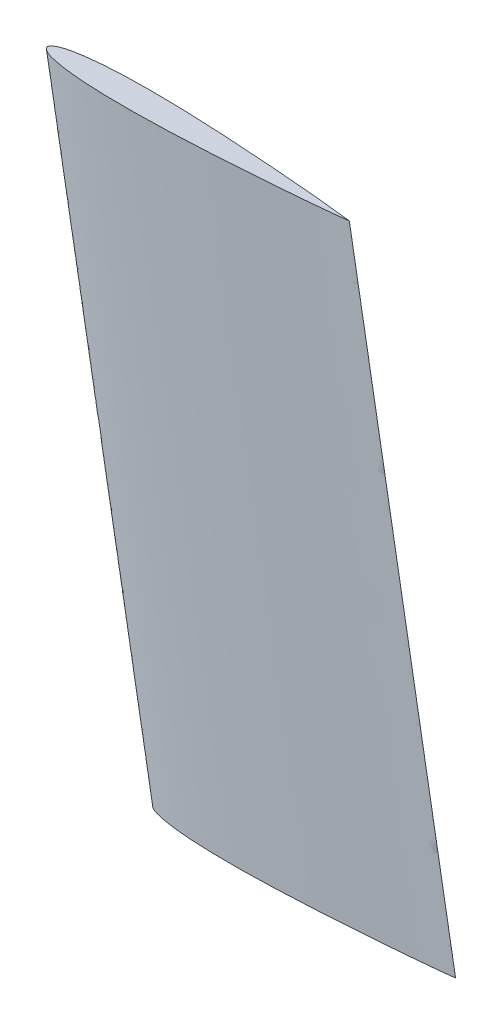
SolidWorks part; units mm, degrees
ref_plane "Front Plane" through (0, 0, 0) normal (0, 0, 1) x (1, 0, 0)
ref_plane "Top Plane" through (0, 0, 0) normal (0, 1, 0) x (1, 0, 0)
ref_plane "Right Plane" through (0, 0, 0) normal (1, 0, 0) x (0, 0, -1)
curve "Curve2"
  spline degree 3 poles (245.7346, 0, -0.2359) (248.5694, 0, 0) (245.7346, 0, 0.2359) (243.4112, 0, 0.6292) (237.7674, 0, 1.2323) (230.8332, 0, 1.9808) (221.7981, 0, 2.8592) (211.1903, 0, 3.8286) (199.0563, 0, 4.8702) (185.65, 0, 5.9536) (171.1852, 0, 7.0355) (155.914, 0, 8.0839) (140.0967, 0, 9.0504) (124.0041, 0, 9.8942) (107.9109, 0, 10.5652) (94.6227, 0, 10.9527) (84.1989, 0, 11.1308) (76.6156, 0, 11.194) (69.2347, 0, 11.1852) (62.0877, 0, 11.0901) (55.2058, 0, 10.9234) (48.6191, 0, 10.6715) (42.3552, 0, 10.3437) (36.4402, 0, 9.9323) (30.8991, 0, 9.4444) (25.7573, 0, 8.8756) (21.0365, 0, 8.2367) (16.7549, 0, 7.5443) (12.9305, 0, 6.8014) (9.5757, 0, 6.0106) (6.7064, 0, 5.1453) (4.3287, 0, 4.1895) (2.4645, 0, 3.1349) (1.1239, 0, 2.0336) (0.2866, 0, 1.0243) (-0.1173, 0, 0) (0.2866, 0, -1.0243) (1.1239, 0, -2.0336) (2.4645, 0, -3.1349) (4.3287, 0, -4.1895) (6.7064, 0, -5.1453) (9.5757, 0, -6.0106) (12.9305, 0, -6.8014) (16.7549, 0, -7.5443) (21.0365, 0, -8.2367) (25.7573, 0, -8.8756) (30.8991, 0, -9.4444) (36.4402, 0, -9.9323) (42.3552, 0, -10.3437) (48.6191, 0, -10.6715) (55.2058, 0, -10.9234) (62.0877, 0, -11.0901) (69.2347, 0, -11.1852) (76.6156, 0, -11.194) (84.1989, 0, -11.1308) (94.6227, 0, -10.9527) (107.9109, 0, -10.5652) (124.0041, 0, -9.8942) (140.0967, 0, -9.0504) (155.914, 0, -8.0839) (171.1852, 0, -7.0355) (185.65, 0, -5.9536) (199.0563, 0, -4.8702) (211.1903, 0, -3.8286) (221.7981, 0, -2.8592) (230.8332, 0, -1.9808) (237.7674, 0, -1.2323) (243.4112, 0, -0.6292) (245.7346, 0, -0.2359) (248.5694, 0, 0) (245.7346, 0, 0.2359) knots -0.018944 -0.008488 -0.002133 0 0.002133 0.008488 0.018944 0.033319 0.051356 0.072756 0.097141 0.124097 0.153163 0.183834 0.215589 0.247878 0.280151 0.31186 0.327333 0.342463 0.357187 0.371448 0.385183 0.398331 0.410845 0.422673 0.433769 0.44409 0.453589 0.46224 0.47001 0.476871 0.482833 0.487909 0.492155 0.495592 0.498196 0.5 0.501804 0.504408 0.507845 0.512091 0.517167 0.523129 0.52999 0.53776 0.546411 0.55591 0.566231 0.577327 0.589155 0.601669 0.614817 0.628552 0.642813 0.657537 0.672667 0.68814 0.719849 0.752122 0.784411 0.816166 0.846837 0.875903 0.902859 0.927244 0.948644 0.966681 0.981056 0.991512 0.997867 1 1.002133 1.008488 1.018944 periodic
sketch "Sketch6" plane through (0, 0, 0) normal (0, 1, 0) x (1, 0, 0)
  line L0 (0, 0) -> (248, 0) construction
  spline S0 degree 3 poles (245.7346, -0.2359) (248.5694, 0) (245.7346, 0.2359) (243.4112, 0.6292) (237.7674, 1.2323) (230.8332, 1.9808) (221.7981, 2.8592) (211.1903, 3.8286) (199.0563, 4.8702) (185.65, 5.9536) (171.1852, 7.0355) (155.914, 8.0839) (140.0967, 9.0504) (124.0041, 9.8942) (107.9109, 10.5652) (94.6227, 10.9527) (84.1989, 11.1308) (76.6156, 11.194) (69.2347, 11.1852) (62.0877, 11.0901) (55.2058, 10.9234) (48.6191, 10.6715) (42.3552, 10.3437) (36.4402, 9.9323) (30.8991, 9.4444) (25.7573, 8.8756) (21.0365, 8.2367) (16.7549, 7.5443) (12.9305, 6.8014) (9.5757, 6.0106) (6.7064, 5.1453) (4.3287, 4.1895) (2.4645, 3.1349) (1.1239, 2.0336) (0.2866, 1.0243) (-0.1173, 0) (0.2866, -1.0243) (1.1239, -2.0336) (2.4645, -3.1349) (4.3287, -4.1895) (6.7064, -5.1453) (9.5757, -6.0106) (12.9305, -6.8014) (16.7549, -7.5443) (21.0365, -8.2367) (25.7573, -8.8756) (30.8991, -9.4444) (36.4402, -9.9323) (42.3552, -10.3437) (48.6191, -10.6715) (55.2058, -10.9234) (62.0877, -11.0901) (69.2347, -11.1852) (76.6156, -11.194) (84.1989, -11.1308) (94.6227, -10.9527) (107.9109, -10.5652) (124.0041, -9.8942) (140.0967, -9.0504) (155.914, -8.0839) (171.1852, -7.0355) (185.65, -5.9536) (199.0563, -4.8702) (211.1903, -3.8286) (221.7981, -2.8592) (230.8332, -1.9808) (237.7674, -1.2323) (243.4112, -0.6292) (245.7346, -0.2359) (248.5694, 0) (245.7346, 0.2359) knots -0.018944 -0.008488 -0.002133 0 0.002133 0.008488 0.018944 0.033319 0.051356 0.072756 0.097141 0.124097 0.153163 0.183834 0.215589 0.247878 0.280151 0.31186 0.327333 0.342463 0.357187 0.371448 0.385183 0.398331 0.410845 0.422673 0.433769 0.44409 0.453589 0.46224 0.47001 0.476871 0.482833 0.487909 0.492155 0.495592 0.498196 0.5 0.501804 0.504408 0.507845 0.512091 0.517167 0.523129 0.52999 0.53776 0.546411 0.55591 0.566231 0.577327 0.589155 0.601669 0.614817 0.628552 0.642813 0.657537 0.672667 0.68814 0.719849 0.752122 0.784411 0.816166 0.846837 0.875903 0.902859 0.927244 0.948644 0.966681 0.981056 0.991512 0.997867 1 1.002133 1.008488 1.018944 only from (248, 0) to (248, 0) construction
  spline S1 degree 3 poles (245.7346, -0.2359) (248.5694, 0) (245.7346, 0.2359) (243.4112, 0.6292) (237.7674, 1.2323) (230.8332, 1.9808) (221.7981, 2.8592) (211.1903, 3.8286) (199.0563, 4.8702) (185.65, 5.9536) (171.1852, 7.0355) (155.914, 8.0839) (140.0967, 9.0504) (124.0041, 9.8942) (107.9109, 10.5652) (94.6227, 10.9527) (84.1989, 11.1308) (76.6156, 11.194) (69.2347, 11.1852) (62.0877, 11.0901) (55.2058, 10.9234) (48.6191, 10.6715) (42.3552, 10.3437) (36.4402, 9.9323) (30.8991, 9.4444) (25.7573, 8.8756) (21.0365, 8.2367) (16.7549, 7.5443) (12.9305, 6.8014) (9.5757, 6.0106) (6.7064, 5.1453) (4.3287, 4.1895) (2.4645, 3.1349) (1.1239, 2.0336) (0.2866, 1.0243) (-0.1173, 0) (0.2866, -1.0243) (1.1239, -2.0336) (2.4645, -3.1349) (4.3287, -4.1895) (6.7064, -5.1453) (9.5757, -6.0106) (12.9305, -6.8014) (16.7549, -7.5443) (21.0365, -8.2367) (25.7573, -8.8756) (30.8991, -9.4444) (36.4402, -9.9323) (42.3552, -10.3437) (48.6191, -10.6715) (55.2058, -10.9234) (62.0877, -11.0901) (69.2347, -11.1852) (76.6156, -11.194) (84.1989, -11.1308) (94.6227, -10.9527) (107.9109, -10.5652) (124.0041, -9.8942) (140.0967, -9.0504) (155.914, -8.0839) (171.1852, -7.0355) (185.65, -5.9536) (199.0563, -4.8702) (211.1903, -3.8286) (221.7981, -2.8592) (230.8332, -1.9808) (237.7674, -1.2323) (243.4112, -0.6292) (245.7346, -0.2359) (248.5694, 0) (245.7346, 0.2359) knots -0.018944 -0.008488 -0.002133 0 0.002133 0.008488 0.018944 0.033319 0.051356 0.072756 0.097141 0.124097 0.153163 0.183834 0.215589 0.247878 0.280151 0.31186 0.327333 0.342463 0.357187 0.371448 0.385183 0.398331 0.410845 0.422673 0.433769 0.44409 0.453589 0.46224 0.47001 0.476871 0.482833 0.487909 0.492155 0.495592 0.498196 0.5 0.501804 0.504408 0.507845 0.512091 0.517167 0.523129 0.52999 0.53776 0.546411 0.55591 0.566231 0.577327 0.589155 0.601669 0.614817 0.628552 0.642813 0.657537 0.672667 0.68814 0.719849 0.752122 0.784411 0.816166 0.846837 0.875903 0.902859 0.927244 0.948644 0.966681 0.981056 0.991512 0.997867 1 1.002133 1.008488 1.018944 only from (248, 0) to (248, 0)
  point P2 (0, 0)
ref_plane "Plane4" through (0, 495, 0) normal (0, 1, 0) x (1, 0, 0)
sketch "Sketch8" plane through (0, 0, 0) normal (0, 0, 1) x (1, 0, 0)
  line L0 (0, 0) -> (-87.2819, 495)
  line L1 (248, 0) -> (160.7181, 495)
  line L2 (248, 0) -> (0, 0) construction
  dimension "D1" = 80
  dimension "D2" = 80
  dimension "D3" = 495
  dimension "D4" = 495
sketch "Sketch9" plane through (0, 495, 0) normal (0, 1, 0) x (1, 0, 0)
  line L0 (160.7181, 0) -> (-87.2819, 0) construction
  spline S2 degree 3 poles (158.4527, -0.2359) (161.2875, 0) (158.4527, 0.2359) (156.1293, 0.6292) (150.4855, 1.2323) (143.5514, 1.9808) (134.5162, 2.8592) (123.9084, 3.8286) (111.7744, 4.8702) (98.3682, 5.9536) (83.9033, 7.0355) (68.6322, 8.0839) (52.8148, 9.0504) (36.7222, 9.8942) (20.6291, 10.5652) (7.3409, 10.9527) (-3.0829, 11.1308) (-10.6663, 11.194) (-18.0472, 11.1852) (-25.1942, 11.0901) (-32.076, 10.9234) (-38.6627, 10.6715) (-44.9266, 10.3437) (-50.8417, 9.9323) (-56.3828, 9.4444) (-61.5245, 8.8756) (-66.2454, 8.2367) (-70.5269, 7.5443) (-74.3513, 6.8014) (-77.7061, 6.0106) (-80.5755, 5.1453) (-82.9532, 4.1895) (-84.8174, 3.1349) (-86.158, 2.0336) (-86.9952, 1.0243) (-87.3992, 0) (-86.9952, -1.0243) (-86.158, -2.0336) (-84.8174, -3.1349) (-82.9532, -4.1895) (-80.5755, -5.1453) (-77.7061, -6.0106) (-74.3513, -6.8014) (-70.5269, -7.5443) (-66.2454, -8.2367) (-61.5245, -8.8756) (-56.3828, -9.4444) (-50.8417, -9.9323) (-44.9266, -10.3437) (-38.6627, -10.6715) (-32.076, -10.9234) (-25.1942, -11.0901) (-18.0472, -11.1852) (-10.6663, -11.194) (-3.0829, -11.1308) (7.3409, -10.9527) (20.6291, -10.5652) (36.7222, -9.8942) (52.8148, -9.0504) (68.6322, -8.0839) (83.9033, -7.0355) (98.3682, -5.9536) (111.7744, -4.8702) (123.9084, -3.8286) (134.5162, -2.8592) (143.5514, -1.9808) (150.4855, -1.2323) (156.1293, -0.6292) (158.4527, -0.2359) (161.2875, 0) (158.4527, 0.2359) knots -0.018944 -0.008488 -0.002133 0 0.002133 0.008488 0.018944 0.033319 0.051356 0.072756 0.097141 0.124097 0.153163 0.183834 0.215589 0.247878 0.280151 0.31186 0.327333 0.342463 0.357187 0.371448 0.385183 0.398331 0.410845 0.422673 0.433769 0.44409 0.453589 0.46224 0.47001 0.476871 0.482833 0.487909 0.492155 0.495592 0.498196 0.5 0.501804 0.504408 0.507845 0.512091 0.517167 0.523129 0.52999 0.53776 0.546411 0.55591 0.566231 0.577327 0.589155 0.601669 0.614817 0.628552 0.642813 0.657537 0.672667 0.68814 0.719849 0.752122 0.784411 0.816166 0.846837 0.875903 0.902859 0.927244 0.948644 0.966681 0.981056 0.991512 0.997867 1 1.002133 1.008488 1.018944 only from (160.7181, 0) to (160.7181, 0)
loft "Loft3" add profiles "Sketch6", "Sketch9" connector at (248, 0, 0) connector at (160.7181, 495, 0)
